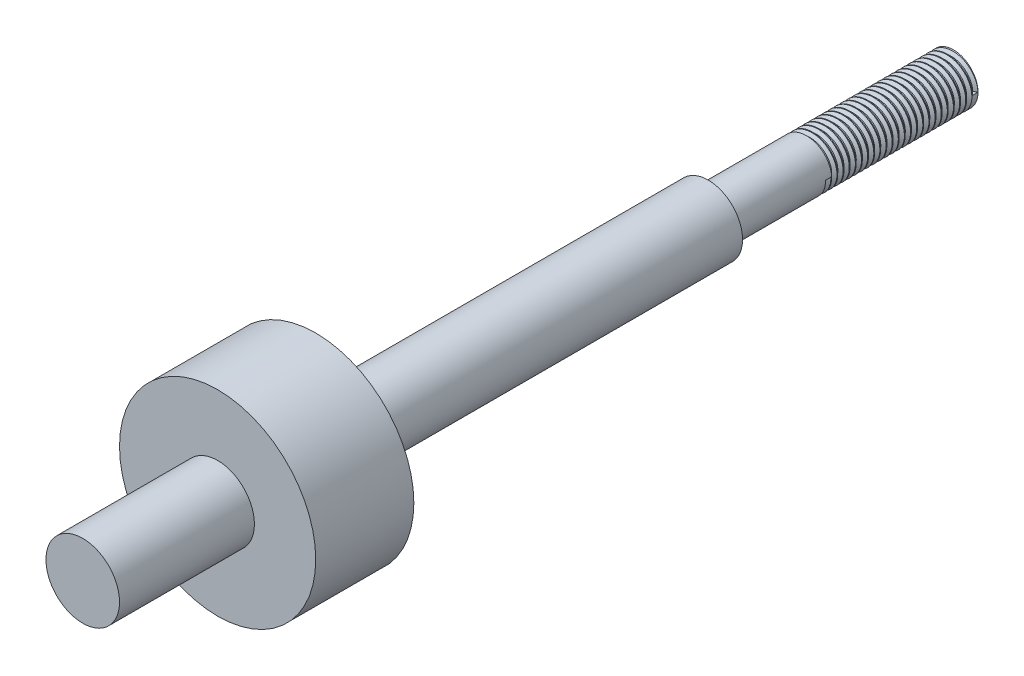
SolidWorks part; units mm, degrees
ref_plane "Спереди" through (0, 0, 0) normal (0, 0, 1) x (1, 0, 0)
ref_plane "Сверху" through (0, 0, 0) normal (0, 1, 0) x (1, 0, 0)
ref_plane "Справа" through (0, 0, 0) normal (1, 0, 0) x (0, 0, -1)
sketch "Эскиз1" plane through (0, 0, 0) normal (0, 0, 1) x (1, 0, 0)
  circle A0 centre (0, 0) radius 1
  dimension "D1" = 2
extrude "Бобышка-Вытянуть1" add sketch "Эскиз1" along normal blind 10
sketch "Эскиз2" plane through (0, 0, 10) normal (0, 0, 1) x (1, 0, 0)
  circle A0 centre (0, 0) radius 1.4
  dimension "D1" = 2.8
extrude "Бобышка-Вытянуть2" add sketch "Эскиз2" along normal blind 16
sketch "Эскиз3" plane through (0, 0, 26) normal (0, 0, 1) x (1, 0, 0)
  circle A0 centre (0, 0) radius 4
  dimension "D1" = 8
extrude "Бобышка-Вытянуть3" add sketch "Эскиз3" along normal blind 4
sketch "Эскиз4" plane through (0, 0, 30) normal (0, 0, 1) x (1, 0, 0)
  circle A0 centre (0, 0) radius 1.5
  dimension "D1" = 3
extrude "Бобышка-Вытянуть4" add sketch "Эскиз4" along normal blind 5.5
thread "Резьба1" pitch 0.25 method cut profile "Профиль резьбы2" start angle 0, offset 0, length 6, pitch 0.25, diameter 2
ref_plane "Плоскость2" through (1, 0, 0) normal (0, -1, 0) x (1, 0, 0)
sketch "Профиль резьбы2" plane through (1, 0, 0) normal (0, -1, 0) x (1, 0, 0)
  line L0 (0, 0) -> (0, 0.25) construction
  line L11 (0, 0) -> (0, 0.2187)
  line L12 (0, 0.2187) -> (-0.1353, 0.1406)
  line L13 (-0.1353, 0.1406) -> (-0.1353, 0.0781)
  line L15 (-0.1353, 0.0781) -> (0, 0)
  line L17 (-0.1353, 0.1094) -> (0, 0.1094) construction
  point P2 (0, 0)
  dimension "Pitch" = 0.25
  dimension "Profile_Angle" = 60
  dimension "Profile_Land" = 0.0625
  dimension "Profile_Height" = 0.1353
